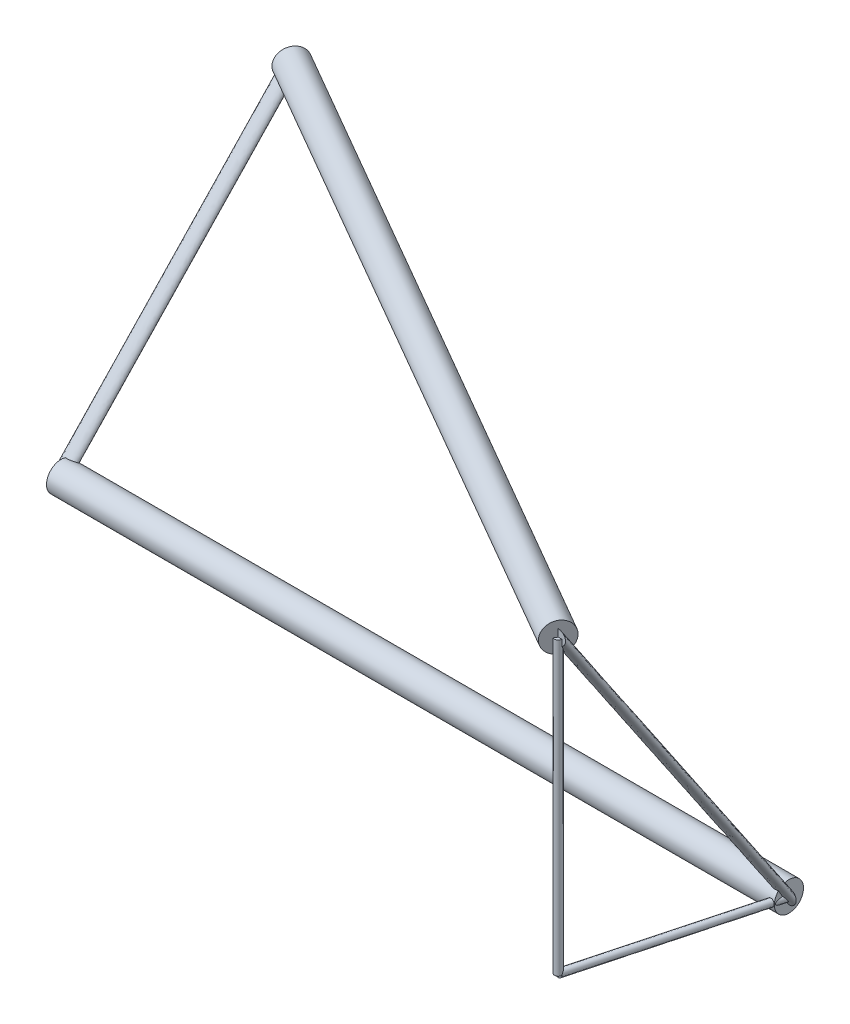
SolidWorks part; units mm, degrees
ref_plane "Front Plane" through (0, 0, 0) normal (0, 0, 1) x (1, 0, 0)
ref_plane "Top Plane" through (0, 0, 0) normal (0, 1, 0) x (1, 0, 0)
ref_plane "Right Plane" through (0, 0, 0) normal (1, 0, 0) x (0, 0, -1)
ref_plane "Plane1" through (0, 4, 0) normal (0, 1, 0) x (1, 0, 0)
sketch "BaseCircle" plane through (0, 0, 0) normal (0, 1, 0) x (1, 0, 0)
  line L2 (0, 0) -> (-3, 0)
  line L3 (0, 0.0516) -> (0, 3.0516)
  circle A0 centre (0, 0) radius 5 construction
  dimension "D1" = 10
  dimension "D2" = 3
  dimension "D3" = 3
sketch "TwistAngle" plane through (0, 0, 0) normal (0, 1, 0) x (1, 0, 0)
  line L0 (4.3301, -2.5) -> (-4.3301, 2.5) construction
  line L1 (0, 0) -> (-3, 0) construction
  circle A0 centre (0, 0) radius 5 construction
  dimension "D1" = 30
sketch "Height" plane through (0, 4, 0) normal (0, 1, 0) x (1, 0, 0)
  line L0 (-652.2053, 376.5509) -> (31958.062, -18450.9957) construction
  line L1 (4.3301, -2.5) -> (-4.3301, 2.5) construction
  dimension "D1" = 0
sketch "Sketch7" plane through (0, 0, 0) normal (0, 0, 1) x (1, 0, 0)
  line L0 (0, -1000) -> (0, 49000)
ref_axis "Axis3" through (0, -4.773, 0) along (0, 1, 0)
sketch "Sketch20" plane through (0, 0, 0) normal (0, 1, 0) x (1, 0, 0)
  line L0 (0, -3) -> (0, 0) construction
  line L1 (0, 0) -> (3, 0) construction
  point P0 (0, 0)
  dimension "D1" = 3
  dimension "D2" = 3
sketch "Sketch13" plane through (0, 0, 0) normal (0, 0, 1) x (1, 0, 0)
  line L0 (0, 0) -> (0, 8)
  line L1 (0, -4.773) -> (0, 7.0643) construction
  dimension "D1" = 8
sketch "Sketch21" plane through (0, 0, 0) normal (1, 0, 0) x (0, 0, -1)
  circle A0 centre (0, 0) radius 0.2
  dimension "D1" = 0.4
extrude "Boss-Extrude1" add sketch "Sketch21" along normal blind 5 and the other way blind 5
ref_plane "Plane2" [suppressed] through (0, 0, 0) normal (0.7071, 0, -0.7071) x (-0.7071, 0, -0.7071)
sketch "Sketch30" plane through (5, 0, 0) normal (1, 0, 0) x (0, 0, -1)
  point P0 (0, 0)
ref_plane "Plane3" through (0, 0, 0) normal (0.866, 0, 0.5) x (0.5, 0, -0.866)
sketch "Sketch32" plane through (0, 0, 0) normal (0.866, 0, 0.5) x (0.5, 0, -0.866)
  circle A0 centre (0, 4) radius 0.2
  point P0 (0, 4)
  dimension "D1" = 0.4
extrude "Boss-Extrude2" add sketch "Sketch32" along normal blind 5 and the other way blind 5 separate body
sketch "Sketch33" plane through (-4.3301, 0, -2.5) normal (-0.866, 0, -0.5) x (-0.5, 0, 0.866)
  point P0 (0, 4)
sketch "Sketch34" plane through (-5, 0, 0) normal (-1, 0, 0) x (0, 0, 1)
  point P0 (0, 0)
ref_plane "Plane4" through (-4.6651, 0, -1.25) normal (-0.9659, 0, -0.2588) x (-0.2588, 0, 0.9659)
sketch "Sketch35" plane through (-4.6651, 0, -1.25) normal (-0.9659, 0, -0.2588) x (-0.2588, 0, 0.9659)
  line L0 (-1.2941, 4) -> (1.2941, 0)
sketch "Sketch38" plane through (4.3301, 0, 2.5) normal (0.866, 0, 0.5) x (0.5, 0, -0.866)
  point P0 (0, 4)
ref_plane "Plane5" through (4.6651, 0, 1.25) normal (0.9659, 0, 0.2588) x (0.2588, 0, -0.9659)
sketch "Sketch39" plane through (4.6651, 0, 1.25) normal (0.9659, 0, 0.2588) x (0.2588, 0, -0.9659)
  line L0 (-1.2941, 4) -> (1.2941, 0)
sketch "Sketch40" plane through (-4.6651, 0, -1.25) normal (-0.9659, 0, -0.2588) x (-0.2588, 0, 0.9659)
  line L0 (-1.2941, 4) -> (-1.2941, 0) construction
sketch "Sketch41" plane through (-4.6651, 0, -1.25) normal (-0.9659, 0, -0.2588) x (-0.2588, 0, 0.9659)
  line L0 (-1.2941, 0) -> (1.2941, 0) construction
sketch "Sketch42" plane through (0, 0, 0) normal (0, 1, 0) x (1, 0, 0)
  line L0 (0, 0) -> (-4.3301, 2.5) construction
sketch "Sketch44" plane through (0, 0, 0) normal (0, 1, 0) x (1, 0, 0)
  line L0 (0, 0) -> (4.3301, -2.5) construction
  line L1 (0, 0) -> (-4.3301, 2.5) construction
  circle A0 centre (0, 0) radius 5 construction
  dimension "D1" = 180
sketch "Sketch45" plane through (4.6651, 0, 1.25) normal (0.9659, 0, 0.2588) x (0.2588, 0, -0.9659)
  line L0 (1.2941, 0) -> (-1.2941, 0)
sketch "Sketch46" plane through (4.6651, 0, 1.25) normal (0.9659, 0, 0.2588) x (0.2588, 0, -0.9659)
  line L0 (-1.2941, 4) -> (-1.2941, 0)
sketch "BaseCircleWithoutAxes" plane through (0, 0, 0) normal (0, 1, 0) x (1, 0, 0)
  circle A0 centre (0, 0) radius 5 construction
  circle A1 centre (0, 0) radius 5 construction
sketch "Sketch48" plane through (0, 0, 0) normal (0, 0, 1) x (1, 0, 0)
  circle A0 centre (-5, 0) radius 0.1
  dimension "D1" = 0.2
sweep "Sweep1" add profiles "Sketch48" path "Sketch35"
sketch "Sketch49" plane through (0, 0, 0) normal (0, 0, 1) x (1, 0, 0)
  circle A0 centre (5, 0) radius 0.1
  dimension "D1" = 0.2
sweep "Sweep2" add profiles "Sketch49" path "Sketch39"
sketch "PointAtAxesCenter" plane through (0, 0, 0) normal (0, 1, 0) x (1, 0, 0)
  point P0 (0, 0)
ref_plane "Plane6" through (0, 6, 0) normal (0, 1, 0) x (1, 0, 0)
sketch "Sketch51" plane through (0, 6, 0) normal (0, 1, 0) x (1, 0, 0)
  arc A0 (0.7216, -0.6923) -> (1, 0) centre (0, 0) cw
  dimension "D1" = 1
sketch "LowerRungAxis" plane through (0, 0, 0) normal (0, 1, 0) x (1, 0, 0)
  line L0 (0, 0) -> (-5, 0) construction
sketch "LowerRungAxisRighthand" plane through (0, 0, 0) normal (0, 1, 0) x (1, 0, 0)
  line L0 (0, 0) -> (5, 0) construction
sketch "Sketch53" plane through (0, 0, 0) normal (0, 1, 0) x (1, 0, 0)
  circle A0 centre (4.3301, -2.5) radius 0.05
  dimension "D1" = 0.1
sweep "Sweep3" add profiles "Sketch53" path "Sketch46"
sketch "Sketch55" plane through (0, 0, 0) normal (0, 0, 1) x (1, 0, 0)
  circle A0 centre (5, 0) radius 0.05
  dimension "D1" = 0.1
sweep "Sweep4" add profiles "Sketch55" path "Sketch45"
sketch "Sketch56" plane through (4.6651, 0, 1.25) normal (0.9659, 0, 0.2588) x (0.2588, 0, -0.9659)
  line L0 (1.2941, 0.06) -> (-1.2941, 4.06)
  line L1 (1.2941, 4) -> (1.2941, 0) construction
  line L2 (-1.2941, 4.1) -> (-1.2941, 4) construction
  line L3 (1.2941, -0.06) -> (-1.2941, 3.94)
  line L4 (-1.2941, 4.06) -> (-1.2941, 3.94)
  line L5 (1.2941, 0.06) -> (1.2941, -0.06)
  dimension "D1" = 0.06
  dimension "D2" = 0.06
  dimension "D3" = 0.06
  dimension "D4" = 0.06
